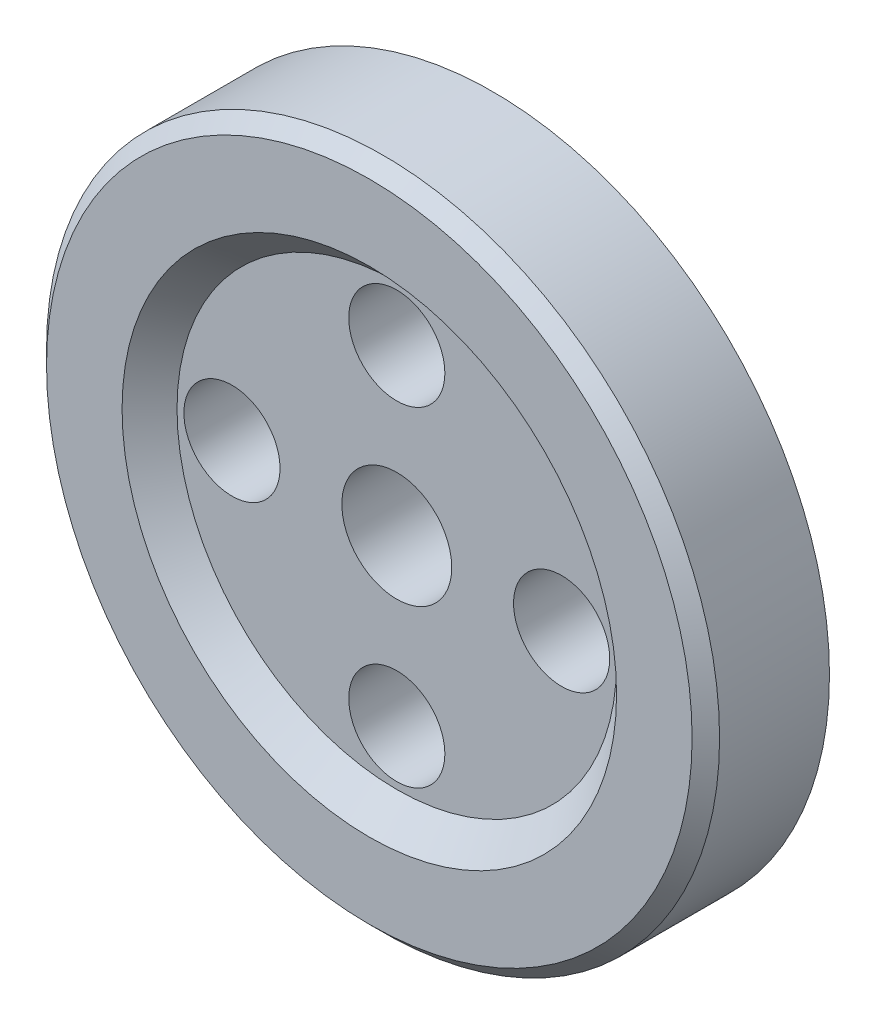
SolidWorks part; units mm, degrees
material "Brass"
ref_plane "Front Plane" through (0, 0, 0) normal (0, 0, 1) x (1, 0, 0)
ref_plane "Top Plane" through (0, 0, 0) normal (0, 1, 0) x (1, 0, 0)
ref_plane "Right Plane" through (0, 0, 0) normal (1, 0, 0) x (0, 0, -1)
sketch "Sketch1" plane through (0, 0, 0) normal (0, 0, 1) x (1, 0, 0)
  circle A0 centre (0, 0) radius 24.5
  circle A1 centre (0, 0) radius 12 construction
  circle A2 centre (0, 12) radius 3.5
  circle A3 centre (-12, 0) radius 3.5
  circle A4 centre (0, -12) radius 3.5
  circle A5 centre (12, 0) radius 3.5
  circle A7 centre (0, 0) radius 4
  dimension "D1" = 49
extrude "Boss-Extrude1" add sketch "Sketch1" along normal mid plane 9
sketch "Sketch2" plane through (0, 0, 4.5) normal (0, 0, 1) x (1, 0, 0)
  circle A0 centre (0, 0) radius 16
  dimension "D1" = 32
extrude "Cut-Extrude1" cut sketch "Sketch2" against normal blind 2
chamfer "Chamfer1" distance 2 angle 45 1 edges at (16, 0, 4.5)
chamfer "Chamfer2" distance 1 angle 45 1 edges at (24.5, 0, 4.5)
